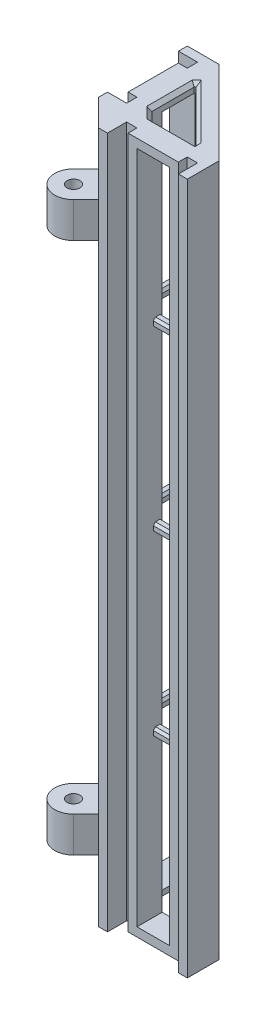
SolidWorks part; units mm, degrees
other "Markup1"
sketch "Sketch17" plane through (-6.4628, 247.65, 6.4628) normal (-0.8928, 0.3948, 0.2171) x (-0.0083, -0.4962, 0.8682)
ref_plane "Front Plane" through (0, 0, 0) normal (0, 0, 1) x (1, 0, 0)
ref_plane "Top Plane" through (0, 0, 0) normal (0, 1, 0) x (1, 0, 0)
ref_plane "Right Plane" through (0, 0, 0) normal (1, 0, 0) x (0, 0, -1)
sketch "Sketch1" plane through (0, 0, 0) normal (0, 1, 0) x (1, 0, 0)
  line L0 (0, 0) -> (34.925, 0) construction
  line L1 (41.275, 0) -> (41.275, 28.575) construction
  line L2 (28.575, 41.275) -> (0, 41.275) construction
  line L3 (0, 41.275) -> (0, 38.1) construction
  line L4 (41.275, 0) -> (41.275, 11.3849)
  line L5 (41.275, 11.3849) -> (11.3849, 41.275)
  line L6 (11.3849, 41.275) -> (0, 41.275)
  line L7 (0, 41.275) -> (0, 38.1)
  line L12 (37.5553, 37.5553) -> (26.3299, 26.3299) construction
  line L13 (0, 34.925) -> (0, 0) construction
  line L15 (34.4, 3.683) -> (34.4, 6.858)
  line L16 (34.4, 6.858) -> (38.1, 6.858)
  line L17 (38.1, 0) -> (38.1, 6.858)
  line L22 (3.683, 34.4) -> (6.858, 34.4)
  line L24 (0, 38.1) -> (6.858, 38.1)
  line L25 (6.858, 34.4) -> (6.858, 38.1)
  line L27 (38.1, 0) -> (41.275, 0) construction
  line L28 (38.1, 0) -> (41.275, 0)
  line L33 (16.4, 6.858) -> (12.7, 6.858)
  line L34 (12.7, 6.858) -> (12.7, 0)
  line L35 (12.7, 0) -> (9.525, 0)
  line L38 (0, 12.7) -> (6.858, 12.7)
  line L39 (6.858, 12.7) -> (6.858, 16.4)
  line L40 (0, 12.7) -> (0, 9.525)
  line L43 (9.525, 0) -> (0, 9.525)
  line L44 (16.4, 6.858) -> (16.4, 3.683)
  line L45 (16.4, 3.683) -> (34.4, 3.683)
  line L46 (6.858, 16.4) -> (3.683, 16.4)
  line L47 (3.683, 16.4) -> (3.683, 34.4)
  arc A2 (41.275, 28.575) -> (28.575, 41.275) centre (28.575, 28.575) ccw construction
  point P9 (16.4, 6.858)
  point P21 (6.858, 16.4)
  point P26 (12.7, 0)
  point P30 (0, 12.7)
  dimension "D4" = 18
  dimension "D9" = 3.175
  dimension "D13" = 12.7
  dimension "D1" = 41.275
  dimension "D2" = 41.275
  dimension "D3" = 3.7
  dimension "D5" = 3.175
  dimension "D6" = 18
  dimension "D7" = 3.175
  dimension "D8" = 6.858
  dimension "D14" = 15.875
  dimension "D15" = 3.175
  dimension "D16" = 6.858
  dimension "D19" = 3.175
  dimension "D20" = 6.858
extrude "Boss-Extrude4" add sketch "Sketch1" along normal blind 247.65 contours L45 L15 L16 L17 L28 L4 L5 L6 L7 L24 L25 L22 L47 L46 L39 L38 L40 L43 L35 L34 L33 L44
sketch "Sketch13" plane through (0, 0, 0) normal (0, -1, 0) x (1, 0, 0)
  line L6 (12.7, -12.7) -> (12.7, -31.75)
  line L7 (12.7, -31.75) -> (31.75, -12.7)
  line L8 (31.75, -12.7) -> (12.7, -12.7)
  line L22 (16.4, -3.683) -> (16.4, -6.858)
  line L23 (16.4, -6.858) -> (12.7, -6.858)
  line L24 (12.7, -6.858) -> (12.7, 0)
  line L25 (12.7, 0) -> (9.525, 0)
  line L26 (9.525, 0) -> (0, -9.525)
  line L27 (0, -9.525) -> (0, -12.7)
  line L28 (0, -12.7) -> (6.858, -12.7)
  line L29 (6.858, -12.7) -> (6.858, -16.4)
  line L30 (6.858, -16.4) -> (3.683, -16.4)
  line L31 (3.683, -16.4) -> (3.683, -34.4)
  line L32 (3.683, -34.4) -> (6.858, -34.4)
  line L33 (6.858, -34.4) -> (6.858, -38.1)
  line L34 (6.858, -38.1) -> (0, -38.1)
  line L35 (0, -38.1) -> (0, -41.275)
  line L36 (0, -41.275) -> (11.3849, -41.275)
  line L37 (11.3849, -41.275) -> (41.275, -11.3849)
  line L38 (41.275, -11.3849) -> (41.275, 0)
  line L39 (41.275, 0) -> (38.1, 0)
  line L40 (38.1, 0) -> (38.1, -6.858)
  line L41 (38.1, -6.858) -> (34.4, -6.858)
  line L42 (34.4, -6.858) -> (34.4, -3.683)
  line L43 (34.4, -3.683) -> (16.4, -3.683)
  line L44 (16.4, -3.683) -> (16.4, -6.858)
  line L45 (16.4, -6.858) -> (12.7, -6.858)
  line L46 (12.7, -6.858) -> (12.7, 0)
  line L47 (12.7, 0) -> (9.525, 0)
  line L48 (9.525, 0) -> (0, -9.525)
  line L49 (0, -9.525) -> (0, -12.7)
  line L50 (0, -12.7) -> (6.858, -12.7)
  line L51 (6.858, -12.7) -> (6.858, -16.4)
  line L52 (6.858, -16.4) -> (3.683, -16.4)
  line L53 (3.683, -16.4) -> (3.683, -34.4)
  line L54 (3.683, -34.4) -> (6.858, -34.4)
  line L55 (6.858, -34.4) -> (6.858, -38.1)
  line L56 (6.858, -38.1) -> (0, -38.1)
  line L57 (0, -38.1) -> (0, -41.275)
  line L58 (0, -41.275) -> (11.3849, -41.275)
  line L59 (11.3849, -41.275) -> (41.275, -11.3849)
  line L60 (41.275, -11.3849) -> (41.275, 0)
  line L61 (41.275, 0) -> (38.1, 0)
  line L62 (38.1, 0) -> (38.1, -6.858)
  line L63 (38.1, -6.858) -> (34.4, -6.858)
  line L64 (34.4, -6.858) -> (34.4, -3.683)
  line L65 (34.4, -3.683) -> (16.4, -3.683)
  point P2 (12.7, -12.7)
  dimension "D2" = 19.05
  dimension "D3" = 90
  dimension "D4" = 19.05
  dimension "D1" = 0
extrude "Cut-Extrude9" cut sketch "Sketch13" against normal up to surface (247.65 mm away) contours L6 L7 L8 up to face at (15.5208, 247.65, -15.5208)
sketch "Sketch11" plane through (3.683, 0, 0) normal (-1, 0, 0) x (0, 0, 1)
  line L1 (-31.225, 3.175) -> (-19.575, 3.175)
  line L2 (-31.225, 3.175) -> (-31.225, 244.475)
  line L3 (-31.225, 244.475) -> (-19.575, 244.475)
  line L4 (-34.4, 0) -> (-16.4, 0)
  line L5 (-16.4, 0) -> (-16.4, 247.65)
  line L6 (-16.4, 247.65) -> (-34.4, 247.65)
  line L7 (-34.4, 247.65) -> (-34.4, 0)
  line L8 (-34.4, 0) -> (-16.4, 0)
  line L9 (-16.4, 0) -> (-16.4, 247.65)
  line L10 (-16.4, 247.65) -> (-34.4, 247.65)
  line L11 (-34.4, 247.65) -> (-34.4, 0)
  line L20 (-19.575, 3.175) -> (-19.575, 244.475)
  line L21 (-31.225, 3.175) -> (-19.575, 244.475) construction
  line L22 (-31.225, 244.475) -> (-19.575, 3.175) construction
  point P2 (-25.4, 3.175)
  point P6 (-25.4, 0)
  point P8 (-25.4, 123.825)
  dimension "D2" = 3.175
  dimension "D3" = 3.175
  dimension "D4" = 3.175
  dimension "D5" = 3.175
  dimension "D1" = 0
extrude "Cut-Extrude7" cut sketch "Sketch11" against normal up to surface (9.017 mm away) contours L3 L20 L1 L2 up to face at (12.7, 123.825, -22.225)
sketch "Sketch12" plane through (0, 0, -3.683) normal (0, 0, 1) x (1, 0, 0)
  line L1 (31.225, 244.475) -> (19.575, 244.475)
  line L2 (31.225, 244.475) -> (31.225, 3.175)
  line L3 (31.225, 3.175) -> (19.575, 3.175)
  line L4 (16.4, 0) -> (34.4, 0)
  line L5 (34.4, 0) -> (34.4, 247.65)
  line L6 (34.4, 247.65) -> (16.4, 247.65)
  line L7 (16.4, 247.65) -> (16.4, 0)
  line L8 (16.4, 0) -> (34.4, 0)
  line L9 (34.4, 0) -> (34.4, 247.65)
  line L10 (34.4, 247.65) -> (16.4, 247.65)
  line L11 (16.4, 247.65) -> (16.4, 0)
  line L12 (19.575, 244.475) -> (19.575, 3.175)
  line L13 (31.225, 244.475) -> (19.575, 3.175) construction
  line L14 (31.225, 3.175) -> (19.575, 244.475) construction
  point P2 (25.4, 0)
  point P4 (25.4, 123.825)
  dimension "D2" = 3.175
  dimension "D3" = 3.175
  dimension "D4" = 3.175
  dimension "D5" = 3.175
  dimension "D1" = 0
extrude "Cut-Extrude8" cut sketch "Sketch12" against normal up to surface (9.017 mm away) contours L1 L12 L3 L2 up to face at (22.225, 123.825, -12.7)
ref_plane "Plane1" through (0, 225.425, 0) normal (0, 1, 0) x (1, 0, 0)
sketch "Sketch16" plane through (0, 225.425, 0) normal (0, 1, 0) x (1, 0, 0)
  line L0 (9.525, 0) -> (0, 9.525) construction
  line L1 (9.525, 0) -> (0, 9.525)
  line L2 (9.525, 0) -> (5.0349, -4.4901)
  line L3 (0, 9.525) -> (-4.4901, 5.0349)
  line L4 (-4.4901, 5.0349) -> (5.0349, -4.4901)
  circle A0 centre (0.2724, 0.2724) radius 2.286
  arc A1 (-4.4901, 5.0349) -> (5.0349, -4.4901) centre (0.2724, 0.2724) ccw
  point P2 (0.2724, 0.2724)
  dimension "D4" = 6.7352
  dimension "D5" = 4.572
  dimension "D1" = 6.35
  dimension "D2" = 90
  dimension "D3" = 6.35
extrude "Boss-Extrude5" add sketch "Sketch16" against normal blind 12.7 contours A0 L4 L2 L1 L3 | L4 A1 A0
ref_plane "Plane2" through (0, 123.825, 0) normal (0, 1, 0) x (1, 0, 0)
mirror "Mirror1" about plane through (0, 123.825, 0) normal (0, 1, 0) of "Boss-Extrude5"
ref_plane "Plane3" through (0, 123.825, 0) normal (0, 1, 0) x (1, 0, 0)
ref_plane "Plane4" through (0, 185.7375, 0) normal (0, 1, 0) x (1, 0, 0)
chamfer "Chamfer1" distance 0.6985 angle 45 2 edges at (31.75, 123.825, -12.7) (12.7, 123.825, -31.75)
chamfer "Chamfer2" distance 3.175 angle 45 1 edges at (12.7, 123.825, -12.7)
chamfer "Chamfer3" distance 1.27 angle 45 12 edges at (31.2561, 0, -12.947) (23.5655, 0, -12.7) (14.2875, 0, -14.2875) (12.7, 0, -23.4632) (12.8746, 0, -31.2261) (22.1527, 0, -22.2973) (14.2875, 247.65, -14.2875) (12.7, 247.65, -23.4632) (12.8746, 247.65, -31.2261) (23.5655, 247.65, -12.7) (31.2561, 247.65, -12.947) (22.1527, 247.65, -22.2973)
sketch "Sketch19" plane through (0, 123.825, 0) normal (0, 1, 0) x (1, 0, 0)
  line L0 (19.575, 12.7) -> (31.225, 12.7) construction
  line L1 (12.7, 19.575) -> (12.7, 31.0515) construction
  line L2 (19.575, 12.7) -> (31.225, 12.7)
  line L3 (12.7, 19.575) -> (12.7, 31.0515)
  line L4 (31.225, 12.7) -> (31.225, 9.525)
  line L5 (12.7, 19.575) -> (9.525, 19.575)
  line L6 (31.225, 9.525) -> (19.575, 9.525)
  line L7 (19.575, 9.525) -> (19.575, 12.7)
  line L8 (9.525, 19.575) -> (9.525, 31.0515)
  line L9 (9.525, 31.0515) -> (12.7, 31.0515)
  dimension "D1" = 3.175
extrude "Boss-Extrude6" add sketch "Sketch19" along normal blind 1.5875 and the other way blind 1.5875
sketch "Sketch20" plane through (0, 185.7375, 0) normal (0, 1, 0) x (1, 0, 0)
  line L0 (9.525, 19.575) -> (12.7, 19.575) construction
  line L1 (12.7, 19.575) -> (12.7, 31.0515) construction
  line L2 (12.7, 31.0515) -> (9.525, 31.0515) construction
  line L3 (9.525, 31.0515) -> (9.525, 19.575) construction
  line L4 (19.575, 12.7) -> (19.575, 9.525) construction
  line L5 (19.575, 9.525) -> (31.225, 9.525) construction
  line L6 (31.225, 9.525) -> (31.225, 12.7) construction
  line L7 (31.225, 12.7) -> (19.575, 12.7) construction
  line L8 (9.525, 19.575) -> (12.7, 19.575)
  line L9 (12.7, 19.575) -> (12.7, 31.0515)
  line L10 (12.7, 31.0515) -> (9.525, 31.0515)
  line L11 (9.525, 31.0515) -> (9.525, 19.575)
  line L12 (19.575, 12.7) -> (19.575, 9.525)
  line L13 (19.575, 9.525) -> (31.225, 9.525)
  line L14 (31.225, 9.525) -> (31.225, 12.7)
  line L15 (31.225, 12.7) -> (19.575, 12.7)
extrude "Boss-Extrude7" add sketch "Sketch20" along normal blind 3.175
mirror "Mirror2" about plane through (0, 123.825, 0) normal (0, 1, 0) of "Boss-Extrude7"
chamfer "Chamfer4" distance 0.7937 angle 45 24 edges at (12.7, 185.7375, -25.3133) (12.7, 122.2375, -25.3133) (25.4, 185.7375, -12.7) (25.4, 122.2375, -12.7) (25.4, 58.7375, -12.7) (12.7, 58.7375, -25.3133) (9.525, 122.2375, -25.3133) (9.525, 125.4125, -25.3133) (12.7, 125.4125, -25.3133) (12.7, 61.9125, -25.3133) (9.525, 61.9125, -25.3133) (9.525, 58.7375, -25.3133) (25.4, 58.7375, -9.525) (25.4, 61.9125, -9.525) (25.4, 61.9125, -12.7) (25.4, 125.4125, -12.7) (25.4, 125.4125, -9.525) (25.4, 122.2375, -9.525) (25.4, 185.7375, -9.525) (25.4, 188.9125, -9.525) (25.4, 188.9125, -12.7) (12.7, 188.9125, -25.3133) (9.525, 188.9125, -25.3133) (9.525, 185.7375, -25.3133)
